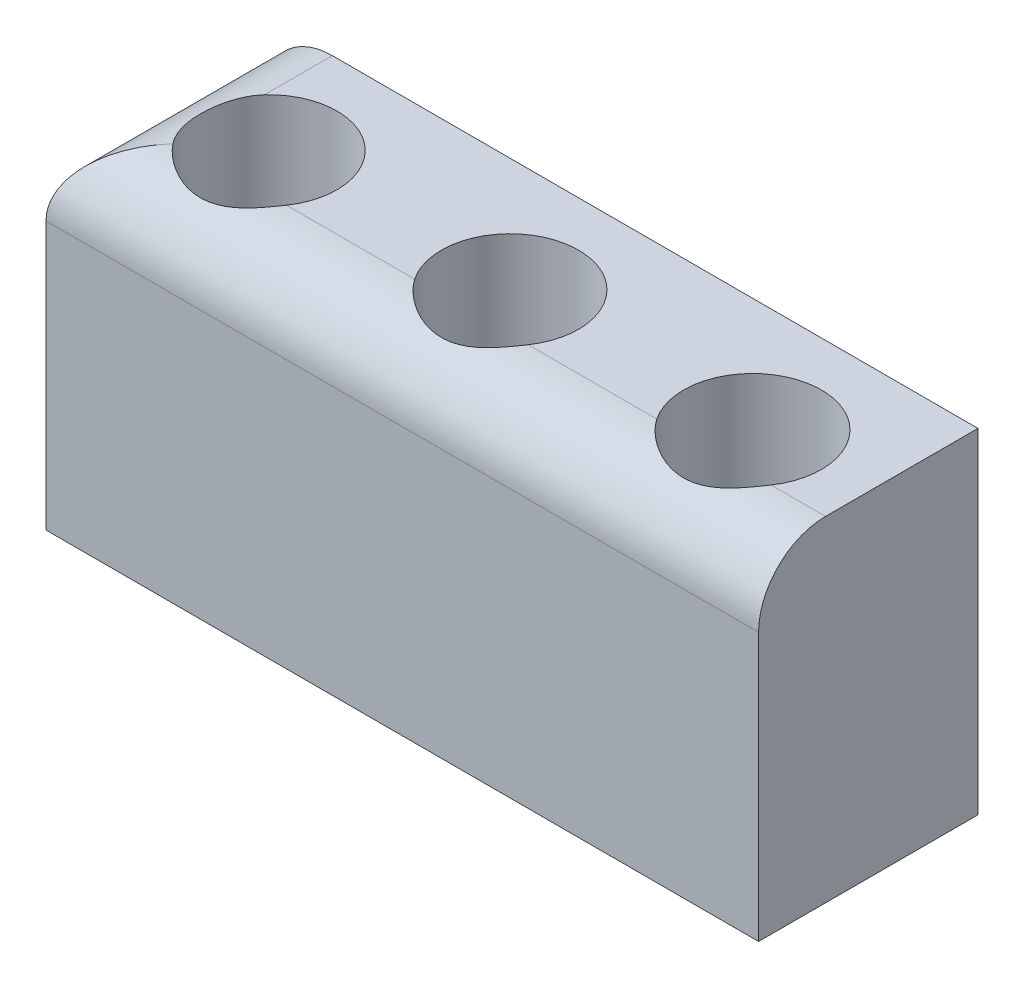
SolidWorks part; units mm, degrees
ref_plane "Front Plane" through (0, 0, 0) normal (0, 0, 1) x (1, 0, 0)
ref_plane "Top Plane" through (0, 0, 0) normal (0, 1, 0) x (1, 0, 0)
ref_plane "Right Plane" through (0, 0, 0) normal (1, 0, 0) x (0, 0, -1)
sketch "Sketch1" plane through (0, 0, 0) normal (0, 1, 0) x (1, 0, 0)
  line L1 (0, 0) -> (21.2932, 0)
  line L2 (0, 0) -> (0, 6.5562)
  line L3 (0, 6.5562) -> (21.2932, 6.5562)
  line L4 (21.2932, 0) -> (21.2932, 6.5562)
  circle A0 centre (10.7125, 3.1522) radius 2.05
  circle A1 centre (3.5025, 3.1522) radius 2.04
  circle A2 centre (17.9595, 3.1522) radius 2.06
  point P11 (3.3336, 3.1522)
  point P12 (10.6583, 3.1522)
  point P13 (3.451, 14.4444)
  point P14 (17.9595, 3.1522)
  point P15 (12.012, 3.1522)
  point P16 (3.5025, 3.1522)
  point P17 (10.7125, 3.1522)
  dimension "D1" = 4.1
  dimension "D2" = 4.08
  dimension "D3" = 4.12
extrude "Boss-Extrude1" add sketch "Sketch1" along normal blind 10 contours L1 L4 L3 L2 A2 A1 A0 region at (0.2228, 0, -3.2781)
fillet "Fillet1" radius 2 2 edges at (10.6466, 10, 0) (0, 10, -3.2781)
